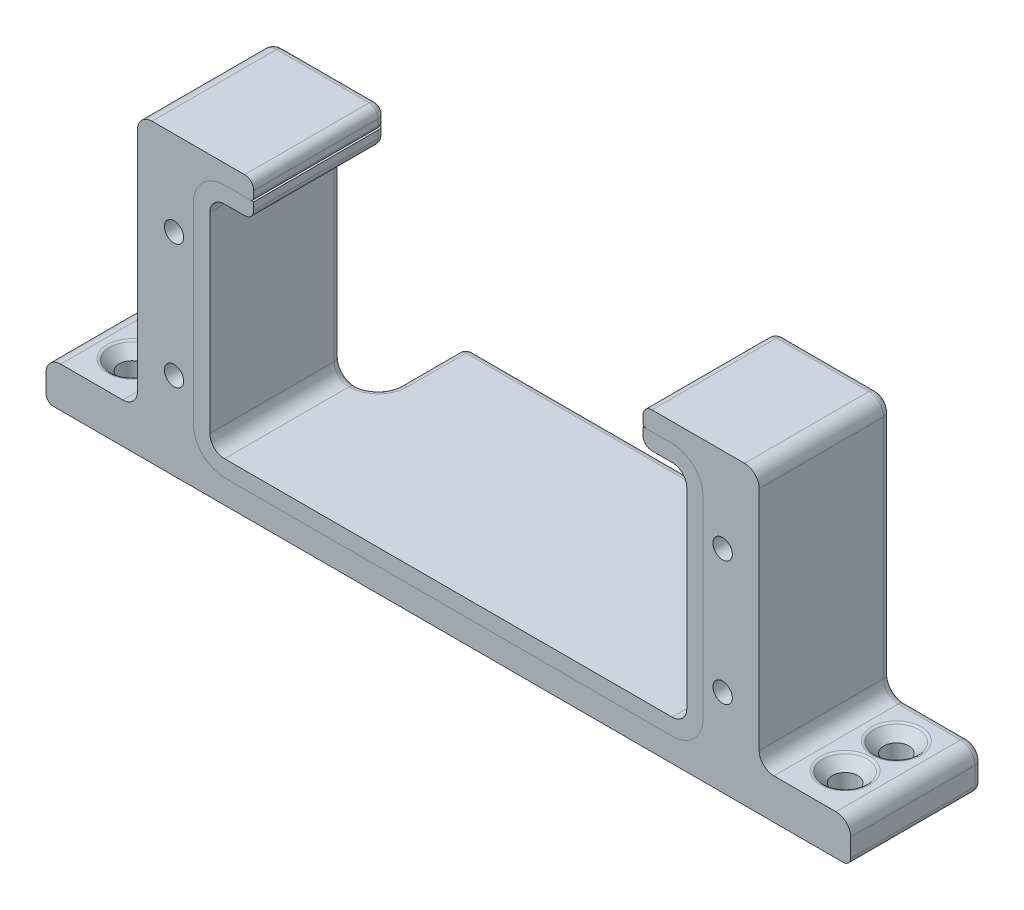
SolidWorks part; units mm, degrees
ref_plane "Front Plane" through (0, 0, 0) normal (0, 0, 1) x (1, 0, 0)
ref_plane "Top Plane" through (0, 0, 0) normal (0, 1, 0) x (1, 0, 0)
ref_plane "Right Plane" through (0, 0, 0) normal (1, 0, 0) x (0, 0, -1)
sketch "Sketch1" plane through (0, 0, 0) normal (0, 0, 1) x (1, 0, 0)
  line L0 (-37.5, 8.6498) -> (-37.5, -8.3502) construction
  line L1 (-42.5, -20.25) -> (42.5, -20.25)
  line L2 (-42.5, -20.25) -> (-42.5, 20.25)
  line L3 (-42.5, 20.25) -> (-32.6, 20.25)
  line L4 (42.5, -20.25) -> (42.5, 20.25)
  line L5 (-42.5, -20.25) -> (42.5, 20.25) construction
  line L6 (-42.5, 20.25) -> (42.5, -20.25) construction
  line L7 (0, 0) -> (0, 22.6037) construction
  line L8 (-32.6, 20.25) -> (-32.6, -14.75)
  line L9 (-32.6, -14.75) -> (32.6, -14.75)
  line L10 (32.6, -14.75) -> (32.6, 20.25)
  line L11 (32.6, 20.25) -> (42.5, 20.25)
  line L12 (0, 0) -> (-32.6, 0) construction
  line L13 (0, 0) -> (32.6, 0) construction
  line L14 (37.5, 8.6498) -> (37.5, -8.3502) construction
  circle A0 centre (-37.5, 8.6498) radius 1.325
  circle A1 centre (-37.5, -8.3502) radius 1.325
  circle A2 centre (37.5, -8.3502) radius 1.325
  circle A3 centre (37.5, 8.6498) radius 1.325
  point P0 (0, 0)
  dimension "D1" = 2.65
  dimension "D2" = 5.5
  dimension "D3" = 6.3998
  dimension "D4" = 17
  dimension "D5" = 35
  dimension "D6" = 4.9
  dimension "D7" = 5
  dimension "D8" = 75
extrude "Boss-Extrude1" add sketch "Sketch1" against normal mid plane 18
sketch "Sketch2" plane through (0, 0, 0) normal (1, 0, 0) x (0, 0, -1)
  line L0 (-9, -20.25) -> (-9, 20.25) construction
  line L1 (9, -20.25) -> (-9, -20.25)
  line L2 (9, -20.25) -> (9, -14.75)
  line L3 (9, -14.75) -> (-9, -14.75)
  line L4 (-9, -20.25) -> (-9, -14.75)
extrude "Boss-Extrude2" add sketch "Sketch2" against normal mid plane 110
sketch "Sketch4" plane through (0, -14.75, 0) normal (0, 1, 0) x (1, 0, 0)
  line L0 (0, 0) -> (-48.75, 0) construction
  line L1 (-48.75, -9) -> (-48.75, 9) construction
  line L2 (-55, -9) -> (-42.5, -9) construction
  line L3 (-55, 9) -> (-42.5, 9) construction
  point P10 (-48.75, 3.5)
  dimension "D1" = 3.5
hole_wizard "Tap Drill for #8-32 Tap1" positions "3DSketch1" profile "Sketch5" hole size "#8-32" standard "ANSI Inch" end condition through all
sketch3d "3DSketch1"
  point P0 (-48.75, -14.75, -3.5)
sketch "Sketch5" plane through (-48.75, -14.75, -3.5) normal (1, 0, 0) x (0, 0, 1)
  line L0 (0, 0) -> (0, 5.5)
  line L1 (0, 5.5) -> (1.7272, 5.5)
  line L2 (1.7272, 5.5) -> (1.7272, 1.4478)
  line L3 (1.7272, 1.4478) -> (3.175, 0)
  line L5 (3.175, 0) -> (0, 0)
  line L6 (-1.7272, 1.4478) -> (-3.175, 0) construction
  line L11 (0, -6.35) -> (0, 107.95) construction
  dimension "Thru Hole Dia." = 3.4544
  dimension "Thru Hole Depth" = 5.5
  dimension "Near C'Sink Dia." = 6.35
  dimension "Near C'Sink Angle" = 90
mirror "Mirror1" about plane through (0, 0, 0) normal (0, 0, 1) of "Tap Drill for #8-32 Tap1"
mirror "Mirror2" about plane through (0, 0, 0) normal (1, 0, 0) of "Mirror1", "Tap Drill for #8-32 Tap1"
sketch "Sketch6" plane through (-32.6, 0, 0) normal (1, 0, 0) x (0, 0, -1)
  line L0 (9, -14.75) -> (9, 20.25) construction
  line L1 (-9, 20.25) -> (9, 20.25)
  line L2 (-9, 20.25) -> (-9, 15.4)
  line L3 (-9, 15.4) -> (9, 15.4)
  line L4 (9, 20.25) -> (9, 15.4)
  dimension "D1" = 4.85
extrude "Boss-Extrude3" add sketch "Sketch6" along normal blind 6
mirror "Mirror3" about plane through (0, 0, 0) normal (1, 0, 0) of "Boss-Extrude3"
sketch "Sketch7" plane through (0, 0, -9) normal (0, 0, -1) x (-1, 0, 0)
  line L0 (-32.6, -14.75) -> (32.6, -14.75) construction
  line L1 (-27.6, -14.75) -> (27.6, -14.75)
  line L2 (-27.6, -14.75) -> (-27.6, -20.25)
  line L3 (-27.6, -20.25) -> (27.6, -20.25)
  line L4 (27.6, -14.75) -> (27.6, -20.25)
  line L5 (55, -20.25) -> (-55, -20.25) construction
  line L6 (0, 0) -> (0, -14.75) construction
  line L7 (-32.6, 15.4) -> (-32.6, -14.75) construction
  dimension "D1" = 5
extrude "Boss-Extrude4" add sketch "Sketch7" along normal blind 12
ref_plane "Plane1" through (0, -20.35, 0) normal (0, -1, 0) x (-1, 0, 0)
sketch "Sketch9" plane through (0, -20.35, 0) normal (0, -1, 0) x (-1, 0, 0)
  line L8 (-55, -9) -> (55, -9)
  line L9 (55, -9) -> (55, 9)
  line L10 (55, 9) -> (27.6, 9)
  line L11 (27.6, 9) -> (27.6, 21)
  line L12 (27.6, 21) -> (-27.6, 21)
  line L13 (-27.6, 21) -> (-27.6, 9)
  line L14 (-27.6, 9) -> (-55, 9)
  line L15 (-55, 9) -> (-55, -9)
  line L16 (-55, -9) -> (55, -9)
  line L17 (55, -9) -> (55, 9)
  line L18 (55, 9) -> (27.6, 9)
  line L19 (27.6, 9) -> (27.6, 21)
  line L20 (27.6, 21) -> (-27.6, 21)
  line L21 (-27.6, 21) -> (-27.6, 9)
  line L22 (-27.6, 9) -> (-55, 9)
  line L23 (-55, 9) -> (-55, -9)
  circle A0 centre (-48.75, 3.5) radius 1.7272 construction
  circle A1 centre (-48.75, -3.5) radius 1.7272 construction
  circle A2 centre (48.75, -3.5) radius 1.7272 construction
  circle A3 centre (48.75, 3.5) radius 1.7272 construction
  circle A4 centre (-48.75, -3.5) radius 1.7272
  circle A5 centre (-48.75, 3.5) radius 1.7272
  circle A6 centre (48.75, -3.5) radius 1.7272
  circle A7 centre (48.75, 3.5) radius 1.7272
  dimension "D1" = 0
extrude "Boss-Extrude5" add sketch "Sketch9" along normal blind 5 separate body
fillet "Fillet4" radius 3 2 edges at (27.6, -17.5, -9) (-27.6, -17.5, -9)
fillet "Fillet1" radius 2 10 edges at (55, -14.75, 0) (-55, -14.75, 0) (42.5, 20.25, 0) (-42.5, 20.25, 0) (32.6, -14.75, 0) (42.5, -14.75, 0) (-32.6, -14.75, 0) (-42.5, -14.75, 0) (-32.6, 15.4, 0) (32.6, 15.4, 0)
fillet "Fillet5" radius 1.25 4 edges at (-26.6, 15.4, 0) (-26.6, 20.25, 0) (26.6, 15.4, 0) (26.6, 20.25, 0)
fillet "Fillet2" radius 1 5 edges at (-27.6, -20.25, -16.5) (0, -14.75, -21) (-28.4787, -20.25, -9.8787) (-55, -20.25, 0) (55, -20.25, 0)
fillet "Fillet6" radius 1 43 edges at (27.6, -20.25, -16.5) (0.5, -20.25, -21) (42.3, -20.25, -9) (28.4787, -20.25, -9.8787) (28.4787, -14.75, -9.8787) (-28.4787, -14.75, -9.8787) (-32.6, 0.325, -9) (32.6, 0.325, -9) (48.75, -14.75, -9) (34.175, 20.25, -9) (42.5, 2.75, -9) (41.9142, 19.6642, -9) (54.4142, -15.3358, -9) (-48.75, -14.75, -9) (-42.5, 2.75, -9) (-41.9142, 19.6642, -9) (-54.4142, -15.3358, -9) (-32.0142, -14.1642, -9) (-32.0142, 14.8142, -9) (32.0142, 14.8142, -9) (32.0142, -14.1642, -9) (43.0858, -14.1642, -9) (-43.0858, -14.1642, -9) (-26.6, 17.825, -9) (-34.175, 20.25, -9) (-29.225, 15.4, -9) (-26.9661, 19.8839, -9) (-26.9661, 15.7661, -9) (29.225, 15.4, -9) (26.6, 17.825, -9) (26.9661, 19.8839, -9) (26.9661, 15.7661, -9) (-27.6, -14.75, -16) (-27.6, -17.5, -21) (-27.6, -15.0429, -20.7071) (27.6, -18, -21) (-27.3071, -19.9571, -21) (27.6, -14.75, -16) (27.6, -15.0429, -20.7071) (-55, -18, -9) (55, -18, -9) (54.7071, -19.9571, -9) (-54.7071, -19.9571, -8.7071)
sketch "Sketch8" plane through (0, 0, 9) normal (0, 0, 1) x (1, 0, 0)
  line L5 (-27.85, 17.65) -> (27.85, 17.65)
  line L10 (34.85, -12.75) -> (34.85, 13.4)
  line L11 (30.6, 17.65) -> (27.85, 17.65)
  line L12 (-27.85, 17.65) -> (-30.6, 17.65)
  line L13 (-30.6, -17) -> (30.6, -17)
  line L14 (-34.85, 13.4) -> (-34.85, -12.75)
  line L15 (34.85, -12.75) -> (34.85, 13.4)
  line L16 (30.6, 17.65) -> (27.85, 17.65)
  line L17 (-27.85, 17.65) -> (-30.6, 17.65)
  line L18 (-30.6, -17) -> (30.6, -17)
  line L19 (-34.85, 13.4) -> (-34.85, -12.75)
  arc A8 (30.6, -17) -> (34.85, -12.75) centre (30.6, -12.75) ccw
  arc A9 (34.85, 13.4) -> (30.6, 17.65) centre (30.6, 13.4) ccw
  arc A10 (-30.6, 17.65) -> (-34.85, 13.4) centre (-30.6, 13.4) ccw
  arc A11 (-34.85, -12.75) -> (-30.6, -17) centre (-30.6, -12.75) ccw
  arc A12 (30.6, -17) -> (34.85, -12.75) centre (30.6, -12.75) ccw
  arc A13 (34.85, 13.4) -> (30.6, 17.65) centre (30.6, 13.4) ccw
  arc A14 (-30.6, 17.65) -> (-34.85, 13.4) centre (-30.6, 13.4) ccw
  arc A15 (-34.85, -12.75) -> (-30.6, -17) centre (-30.6, -12.75) ccw
  dimension "D1" = 2.25
split "Split1" trim tools "Sketch8" bodies to split 108 resulting bodies 109 110
fillet "Fillet7" radius 2 8 edges at (-55, -22.85, 9) (-55, -22.85, -9) (-27.6, -22.85, -9) (-27.6, -22.85, -21) (27.6, -22.85, -21) (27.6, -22.85, -9) (55, -22.85, 9) (55, -22.85, -9)
fillet "Fillet8" radius 0.5 40 edges at (54.4142, -25.35, 8.4142) (55, -25.35, 0) (54.4142, -25.35, -8.4142) (41.3, -25.35, -9) (28.1858, -25.35, -9.5858) (27.6, -25.35, -15) (27.0142, -25.35, -20.4142) (0, -25.35, -21) (-27.0142, -25.35, -20.4142) (-27.6, -25.35, -15) (-28.1858, -25.35, -9.5858) (-41.3, -25.35, -9) (-54.4142, -25.35, -8.4142) (-55, -25.35, 0) (-54.4142, -25.35, 8.4142) (54.4142, -20.35, 8.4142) (55, -20.35, 0) (54.4142, -20.35, -8.4142) (41.3, -20.35, -9) (28.1858, -20.35, -9.5858) (27.6, -20.35, -15) (27.0142, -20.35, -20.4142) (0, -20.35, -21) (-27.0142, -20.35, -20.4142) (-27.6, -20.35, -15) (-28.1858, -20.35, -9.5858) (-41.3, -20.35, -9) (-54.4142, -20.35, -8.4142) (-55, -20.35, 0) (-54.4142, -20.35, 8.4142) (0, -25.35, 9) (0, -20.35, 9) (48.75, -20.35, -5.2272) (48.75, -20.35, 1.7728) (48.75, -25.35, -5.2272) (48.75, -25.35, 1.7728) (-48.75, -25.35, -5.2272) (-48.75, -25.35, 1.7728) (-48.75, -20.35, 1.7728) (-48.75, -20.35, -5.2272)
delete or keep bodies "Body-Delete/Keep 1" type delete bodies bodies 111
fillet "Fillet9" radius 0.5 19 edges at (-28.4787, -17, -9.8787) (28.4787, -17, -9.8787) (-27.6, -17, -16) (27.6, -17, -16) (-33.6052, -15.7552, -9) (-34.85, 0.325, -9) (-33.6052, 16.4052, -9) (-29.1, 17.65, -9) (29.1, 17.65, -9) (33.6052, 16.4052, -9) (34.85, 0.325, -9) (33.6052, -15.7552, -9) (-26.6, 17.65, 0.5) (26.6, 17.65, 0.5) (0, -17, -21) (26.8929, 17.65, -8.7071) (-26.8929, 17.65, -8.7071) (27.3071, -17, -20.7071) (-27.3071, -17, -20.7071)
fillet "Fillet10" radius 0.5 4 edges at (-48.75, -14.75, -0.325) (-48.75, -14.75, 6.675) (48.75, -14.75, -0.325) (48.75, -14.75, 6.675)
chamfer "Chamfer1" distance 0.5 angle 45 4 edges at (-36.175, 8.6498, -9) (-36.175, -8.3502, -9) (36.175, -8.3502, -9) (36.175, 8.6498, -9)
